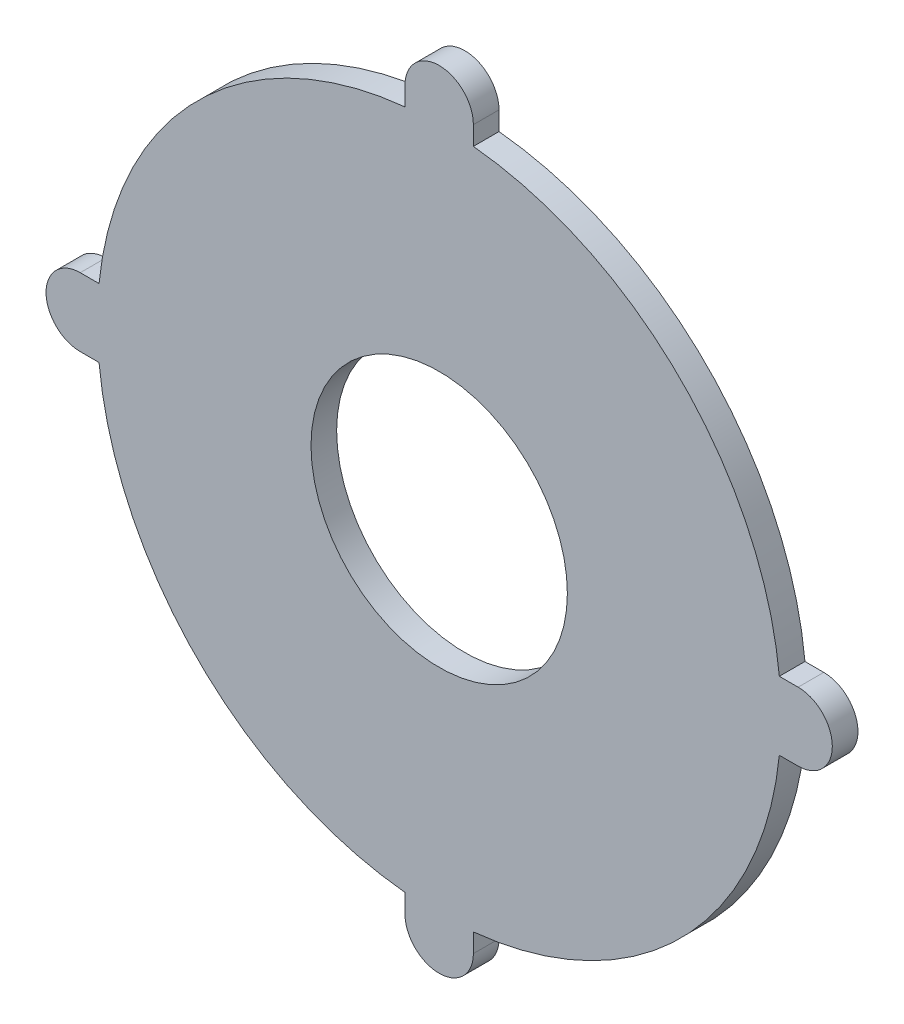
SolidWorks part; units mm, degrees
ref_plane "前视基准面" through (0, 0, 0) normal (0, 0, 1) x (1, 0, 0)
ref_plane "上视基准面" through (0, 0, 0) normal (0, 1, 0) x (1, 0, 0)
ref_plane "右视基准面" through (0, 0, 0) normal (1, 0, 0) x (0, 0, -1)
other "Configuration Table"
sketch "草图1" plane through (0, 0, 0) normal (0, 0, 1) x (1, 0, 0)
  circle A0 centre (0, 0) radius 20
  circle A1 centre (0, 0) radius 7.5
extrude "凸台-拉伸1" add sketch "草图1" along normal blind 1.5
sketch "草图2" plane through (0, 0, 0) normal (0, 0, 1) x (1, 0, 0)
  line L0 (19, -2) -> (21, -2)
  line L1 (21, 2) -> (19, 2)
  line L2 (19, 2) -> (19, -2)
  line L3 (2, 19) -> (2, 21)
  line L4 (-2, 21) -> (-2, 19)
  line L5 (-2, 19) -> (2, 19)
  line L6 (-19, 2) -> (-21, 2)
  line L7 (-21, -2) -> (-19, -2)
  line L8 (-19, -2) -> (-19, 2)
  line L9 (-2, -19) -> (-2, -21)
  line L10 (2, -21) -> (2, -19)
  line L11 (2, -19) -> (-2, -19)
  arc A0 (21, -2) -> (21, 2) centre (21, 0) ccw
  arc A1 (2, 21) -> (-2, 21) centre (0, 21) ccw
  arc A2 (-21, 2) -> (-21, -2) centre (-21, 0) ccw
  arc A3 (-2, -21) -> (2, -21) centre (0, -21) ccw
extrude "凸台-拉伸2" add sketch "草图2" along normal blind 1.5
